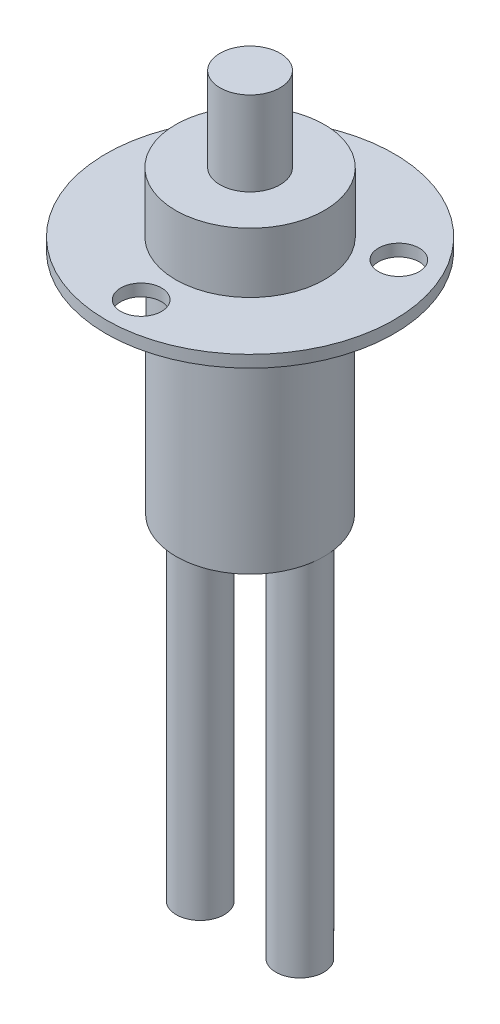
SolidWorks part; units mm, degrees
ref_plane "Front Plane" through (0, 0, 0) normal (0, 0, 1) x (1, 0, 0)
ref_plane "Top Plane" through (0, 0, 0) normal (0, 1, 0) x (1, 0, 0)
ref_plane "Right Plane" through (0, 0, 0) normal (1, 0, 0) x (0, 0, -1)
sketch "Sketch1" plane through (0, 0, 0) normal (0, 1, 0) x (1, 0, 0)
  circle A0 centre (0, 0) radius 6.15
  dimension "D1" = 12.3
extrude "Boss-Extrude1" add sketch "Sketch1" along normal blind 19
sketch "Sketch2" plane through (0, 19, 0) normal (0, 1, 0) x (1, 0, 0)
  circle A0 centre (0, 0) radius 12
  dimension "D1" = 24
extrude "Boss-Extrude2" add sketch "Sketch2" along normal blind 1
sketch "Sketch3" plane through (0, 20, 0) normal (0, 1, 0) x (1, 0, 0)
  circle A0 centre (0, 0) radius 6.2
  dimension "D1" = 12.4
extrude "Boss-Extrude3" add sketch "Sketch3" along normal blind 5
sketch "Sketch4" plane through (0, 25, 0) normal (0, 1, 0) x (1, 0, 0)
  circle A0 centre (0, 0) radius 2.5
  dimension "D1" = 5
extrude "Boss-Extrude4" add sketch "Sketch4" along normal blind 7
sketch "Sketch5" plane through (0, 0, 0) normal (0, -1, 0) x (1, 0, 0)
  circle A0 centre (-4.15, 0) radius 2
  circle A1 centre (4.15, 0) radius 2
  circle A2 centre (0, 0) radius 6.15 construction
  circle A3 centre (0, 0) radius 6.15 construction
  dimension "D1" = 4
extrude "Boss-Extrude5" add sketch "Sketch5" along normal blind 30
sketch "Sketch6" plane through (0, 19, 0) normal (0, -1, 0) x (1, 0, 0)
  circle A0 centre (0, 9.075) radius 1.5
  circle A1 centre (0, 0) radius 12 construction
  arc A2 (6.15, 0) -> (-6.15, 0) centre (0, 0) ccw construction
  circle A3 centre (0, 0) radius 12
  arc A4 (6.15, 0) -> (-6.15, 0) centre (0, 0) ccw
  circle A5 centre (0, 0) radius 9.075 construction
  circle A6 centre (7.8592, -4.5375) radius 1.5
  circle A7 centre (-7.8592, -4.5375) radius 1.5
  point P16 (0, 0)
  dimension "D1" = 3
  dimension "D2" = 24
  dimension "D3" = 6.15
  dimension "D4" = 18.15
  dimension "D5" = 3
extrude "Cut-Extrude1" cut sketch "Sketch6" against normal through all contours A0 | A6 | A7 region at (0, 19, 9.075) region at (7.8592, 19, -4.5375) region at (-7.8592, 19, -4.5375)
hole_wizard "M3 Clearance Hole1" positions "Sketch7" profile "Sketch9" hole size "M3" standard "DIN" end condition through all
sketch "Sketch7" plane through (0, 20, 0) normal (0, 1, 0) x (1, 0, 0)
  point P0 (7.8592, 4.5375)
  point P3 (-7.8592, 4.5375)
  point P6 (0, -9.075)
sketch "Sketch9" plane through (7.8592, 20, -4.5375) normal (1, 0, 0) x (0, 0, 1)
  line L0 (0, 0) -> (0, 50)
  line L1 (0, 50) -> (1.7, 50)
  line L2 (1.7, 50) -> (1.7, 0)
  line L5 (1.7, 0) -> (0, 0)
  line L11 (0, -6.35) -> (0, 107.95) construction
  dimension "Thru Hole Dia." = 3.4
  dimension "Thru Hole Depth" = 50
equation "\"D4@Sketch6\"=(\"D2@Sketch6\"+2*\"D3@Sketch6\")/2"
